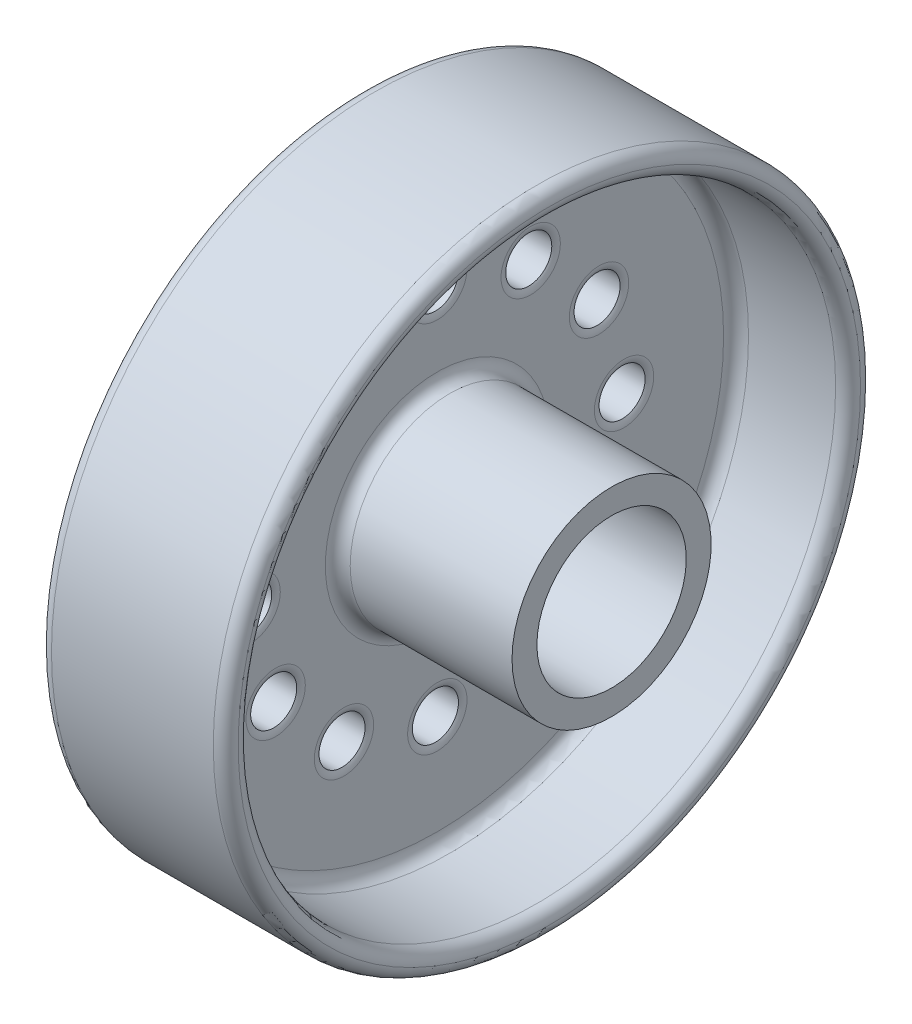
SolidWorks part; units mm, degrees
ref_plane "Front Plane" through (0, 0, 0) normal (0, 0, 1) x (1, 0, 0)
ref_plane "Top Plane" through (0, 0, 0) normal (0, 1, 0) x (1, 0, 0)
ref_plane "Right Plane" through (0, 0, 0) normal (1, 0, 0) x (0, 0, -1)
sketch "Sketch3" plane through (0, 0, 0) normal (0, 0, 1) x (1, 0, 0)
  line L0 (0, 0) -> (157.7295, 0) construction
  line L1 (0, 30) -> (0, 130)
  line L2 (0, 130) -> (75, 130)
  line L3 (75, 130) -> (75, 120)
  line L4 (75, 120) -> (30, 120)
  line L5 (30, 120) -> (30, 40)
  line L6 (30, 40) -> (100, 40)
  line L7 (100, 40) -> (100, 30)
  line L8 (100, 30) -> (0, 30)
  line L9 (0, 0) -> (0, 132.2456) construction
  point P11 (101.8125, 120)
  dimension "D1" = 10
  dimension "D2" = 100
  dimension "D3" = 80
  dimension "D4" = 100
  dimension "D5" = 30
  dimension "D6" = 30
  dimension "D7" = 75
revolve "Revolve1" add sketch "Sketch3" angle 360 about L0 region at (27.5, 77.2892, 0)
sketch "Sketch4" plane through (30, 0, 0) normal (1, 0, 0) x (0, 0, -1)
  line L0 (0, 0) -> (0, 75) construction
  dimension "D1" = 75
hole_wizard "M20x1.5 Tapped Hole1" positions "Sketch5" profile "Sketch6" tap size "M20x1.5" standard "ANSI Metric" end condition through all
sketch "Sketch5" plane through (30, 0, 0) normal (1, 0, 0) x (0, 0, -1)
  point P0 (0, 75)
cosmetic thread "Hole Thread1" parameters "D2"=20
sketch "Sketch6" plane through (30, 75, 0) normal (0, 1, 0) x (0, 0, -1)
  line L0 (0, 0) -> (0, 30)
  line L1 (0, 30) -> (9.25, 30)
  line L2 (9.25, 30) -> (9.25, 0.775)
  line L3 (9.25, 0.775) -> (10.025, 0)
  line L5 (10.025, 0) -> (0, 0)
  line L6 (-9.25, 0.775) -> (-10.025, 0) construction
  line L11 (0, -6.35) -> (0, 107.95) construction
  dimension "Thru Tap Drill Dia." = 18.5
  dimension "Thru Tap Drill Depth" = 30
  dimension "Near C'Sink Dia." = 20.05
  dimension "Near C'Sink Angle" = 90
pattern_circular "CirPattern1" count 12 over 360 about axis through (100, 0, 0) along (-1, 0, 0) of "M20x1.5 Tapped Hole1"
fillet "Fillet1" radius 5 17 edges at (30, 0, 120) (30, 0, 40) (30, 75, -10.025) (30, 64.9519, -47.525) (30, 37.5, -74.9769) (30, 0, -85.025) (30, -37.5, -74.9769) (30, -64.9519, -47.525) (30, -75, -10.025) (30, -64.9519, 27.475) (30, -37.5, 54.9269) (30, 0, 64.975) (30, 37.5, 54.9269) (30, 64.9519, 27.475) (0, 0, 130) (75, 0, 130) (75, 0, 120)
